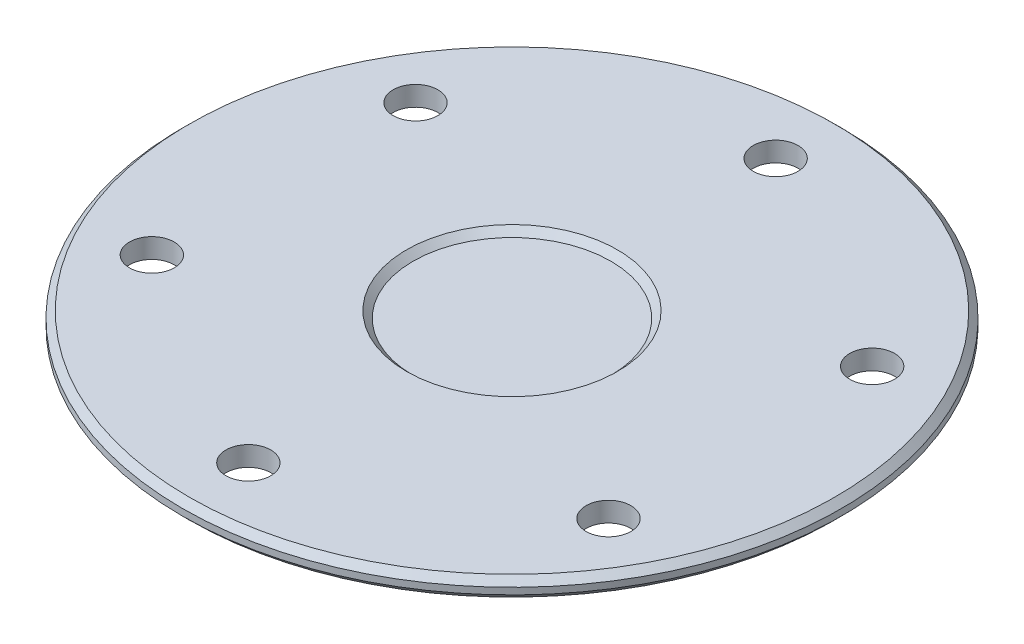
SolidWorks part; units mm, degrees
ref_plane "前视基准面" through (0, 0, 0) normal (0, 0, 1) x (1, 0, 0)
ref_plane "上视基准面" through (0, 0, 0) normal (0, 1, 0) x (1, 0, 0)
ref_plane "右视基准面" through (0, 0, 0) normal (1, 0, 0) x (0, 0, -1)
sketch "草图1" plane through (0, 0, 0) normal (0, 1, 0) x (1, 0, 0)
  circle A0 centre (0, 0) radius 50
  dimension "D1" = 100
extrude "凸台-拉伸1" add sketch "草图1" along normal blind 3
sketch "草图2" plane through (0, 3, 0) normal (0, 1, 0) x (1, 0, 0)
  line L0 (0, 0) -> (0, 52.7951)
  circle A0 centre (0, 0) radius 40
  dimension "D1" = 80
hole_wizard "M8 螺纹孔的螺纹孔钻头1" positions "草图3" profile "草图4" hole size "M8" standard "GB"
sketch "草图3" plane through (0, 3, 0) normal (0, 1, 0) x (1, 0, 0)
  line L0 (0, 0) -> (0, 52.7951) construction
  circle A0 centre (0, 0) radius 40 construction
  point P0 (0, 40)
sketch "草图4" plane through (0, 3, -40) normal (1, 0, 0) x (0, 0, 1)
  line L0 (0, 0) -> (0, 18.0429)
  line L1 (0, 18.0429) -> (3.4, 16)
  line L2 (3.4, 16) -> (3.4, 0)
  line L5 (3.4, 0) -> (0, 0)
  line L10 (0, 18.0429) -> (-3.4, 16) construction
  line L11 (0, -6.35) -> (0, 107.95) construction
  dimension "孔直径" = 6.8
  dimension "孔深度" = 16
  dimension "导头角度" = 118
pattern_circular "阵列(圆周)1" count 6 over 360 about axis through (0, 3, 0) along (0, -1, 0) of "M8 螺纹孔的螺纹孔钻头1"
sketch "草图5" plane through (0, 3, 0) normal (0, 1, 0) x (1, 0, 0)
  circle A0 centre (0, 0) radius 15
  dimension "D1" = 30
extrude "切除-拉伸1" cut sketch "草图5" against normal blind 1
chamfer "倒角1" distance 1 angle 45 3 edges at (0, 0, 50) (0, 3, 50) (0, 3, 15)
